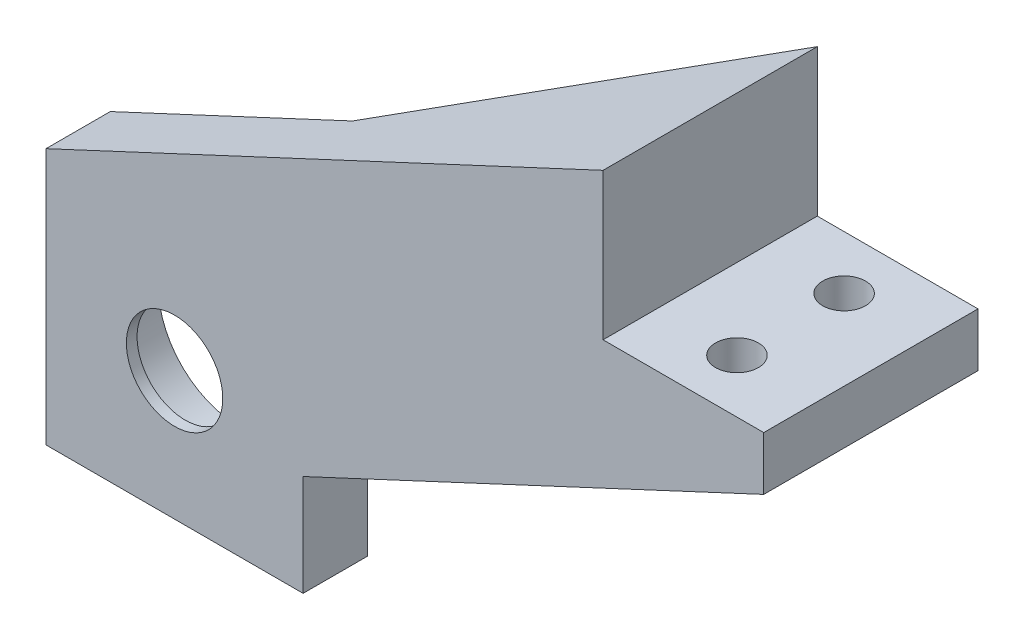
SolidWorks part; units mm, degrees
note: The reader was unsure of these and kept them because the rebuilt part matched: shared geometry of "Sketch1<3>", "Sketch4<3>", "Sketch3<4>".
ref_plane "Front Plane" through (0, 0, 0) normal (0, 0, 1) x (1, 0, 0)
ref_plane "Top Plane" through (0, 0, 0) normal (0, 1, 0) x (1, 0, 0)
ref_plane "Right Plane" through (0, 0, 0) normal (1, 0, 0) x (0, 0, -1)
sketch "Sketch1" plane through (0, 0, 0) normal (0, 0, 1) x (1, 0, 0)
  circle A0 centre (0, 0) radius 7.5
  circle A1 centre (0, 0) radius 4.5
  circle A2 centre (0, 0) radius 10
  dimension "D1" = 15
  dimension "D2" = 20
  dimension "D3" = 9
extrude "Boss-Extrude1" add sketch "Sketch1" against normal up to surface (5 mm away) contours A2 A0
extrude "Boss-Extrude2" add sketch "Sketch1<3>" along normal blind 1 contours A0 A1 | A2 A0
sketch "Sketch1<3>" plane through (0, 0, 0) normal (0, 0, 1) x (1, 0, 0) same geometry as "Sketch1"
sketch "Sketch2" plane through (0, 0, 1) normal (0, 0, 1) x (1, 0, 0)
  line L3 (55, 22.5) -> (40, 22.5)
  line L5 (-12, -0.9326) -> (-12, -12)
  line L6 (-12, -12) -> (12, -12)
  line L8 (40, 22.5) -> (40, 17.5)
  line L13 (40, 17.5) -> (55, 17.5)
  line L14 (55, 17.5) -> (55, 22.5)
  line L15 (-110, 22.5) -> (290, 22.5) construction
  line L16 (10.6203, 22.5) -> (-12, 11.952)
  line L17 (-12, -0.9326) -> (-12, 11.952)
  line L18 (40, 22.5) -> (10.6203, 22.5)
  line L19 (55, 17.5) -> (12, -2.5512)
  line L20 (12, -2.5512) -> (12, -12)
  line L21 (10.6203, 22.5) -> (40, 36.2)
  line L23 (34.1088, 37.8664) -> (-8.8309, 17.8433) construction
  line L24 (40, 22.5) -> (40, 34.2) construction
  line L25 (40, 36.2) -> (40, 22.5)
  circle A1 centre (0, 0) radius 10
  circle A2 centre (0, 0) radius 10 construction
  dimension "D1" = 12
  dimension "D2" = 24
  dimension "D3" = 15
  dimension "D4" = 5
  dimension "D5" = 25
  dimension "D6" = 4
  dimension "D7" = 12
  dimension "D8" = 2
  dimension "D9" = 0
extrude "Boss-Extrude3" add sketch "Sketch2" against normal up to surface (6 mm away) up to face at (-10, 0, -5)
sketch "Sketch3" plane through (0, 22.5, 0) normal (0, -1, 0) x (1, 0, 0)
  line L0 (40, -286) -> (40, 14) construction
  line L1 (55, -5) -> (40, -5)
  line L2 (55, -5) -> (55, -19)
  line L3 (55, -19) -> (40, -19)
  line L4 (40, -5) -> (40, -19)
  line L5 (55, -5) -> (40, -19) construction
  line L6 (55, -19) -> (40, -5) construction
  line L7 (55, 1) -> (12, 1) construction
  line L8 (40, -19) -> (10.6203, -5)
  line L9 (55, -5) -> (55, 1) construction
  line L10 (40, -5) -> (10.6203, -5)
  line L11 (40, -5) -> (-12, -5) construction
  point P4 (47.5, -12)
  point P11 (0, 0)
  point P14 (40, -19)
  point P16 (0, 0)
  dimension "D1" = 20
  dimension "D2" = 29.3797
extrude "Boss-Extrude7" add sketch "Sketch3" along normal up to surface (11.9946 mm away) contours L4 L10 L8 | L1 L4 L3 L2 up to face at (33.5, 7.4744, -2)
sketch "Sketch4" plane through (0, 22.5, 0) normal (0, -1, 0) x (1, 0, 0)
  line L1 (55, 1) -> (40, 1)
  line L2 (55, 1) -> (55, -19)
  line L3 (55, -19) -> (40, -19)
  line L4 (40, 1) -> (40, -19)
  line L5 (55, 1) -> (40, -19) construction
  line L6 (55, -19) -> (40, 1) construction
  line L7 (55, -19) -> (55, 1) construction
  line L8 (55, -9) -> (40, -9) construction
  line L9 (47.5, -9.9585) -> (44, -11.9793)
  line L10 (44, -11.9793) -> (44, -16.0207)
  line L11 (44, -16.0207) -> (47.5, -18.0415)
  line L12 (47.5, -18.0415) -> (51, -16.0207)
  line L13 (51, -16.0207) -> (51, -11.9793)
  line L14 (51, -11.9793) -> (47.5, -9.9585)
  line L21 (51, -6.0207) -> (47.5, -8.0415)
  line L22 (51, -1.9793) -> (51, -6.0207)
  line L23 (47.5, 0.0415) -> (51, -1.9793)
  line L24 (44, -1.9793) -> (47.5, 0.0415)
  line L25 (44, -6.0207) -> (44, -1.9793)
  line L26 (47.5, -8.0415) -> (44, -6.0207)
  line L27 (55, 1) -> (40, 1) construction
  circle A0 centre (47.5, -14) radius 3.5 construction
  circle A1 centre (47.5, -4) radius 3.5 construction
  circle A2 centre (47.5, -14) radius 2
  circle A3 centre (47.5, -4) radius 2
  point P4 (47.5, -9)
  point P28 (45.75, -10.9689)
  point P31 (0, 0)
  dimension "D3" = 4
  dimension "D1" = 7.5
  dimension "D2" = 7
  dimension "D4" = 5
  dimension "D5" = 15
  dimension "D6" = 20
extrude "Cut-Extrude4" cut sketch "Sketch4" along normal through all contours A2 | A3
extrude "Cut-Extrude5" cut sketch "Sketch4<3>" along normal through all from offset 3 contours L26 L21 L22 L23 L24 L25 A3 | L13 L14 L9 L10 L11 L12 A2
sketch "Sketch4<3>" plane through (0, 22.5, 0) normal (0, -1, 0) x (1, 0, 0) same geometry as "Sketch4"
extrude "Boss-Extrude8" add sketch "Sketch3<4>" against normal up to surface (13.7 mm away) contours L4 L10 L8 up to face at (13.3241, 23.7608, -2.6)
sketch "Sketch3<4>" plane through (0, 22.5, 0) normal (0, -1, 0) x (1, 0, 0) same geometry as "Sketch3"
